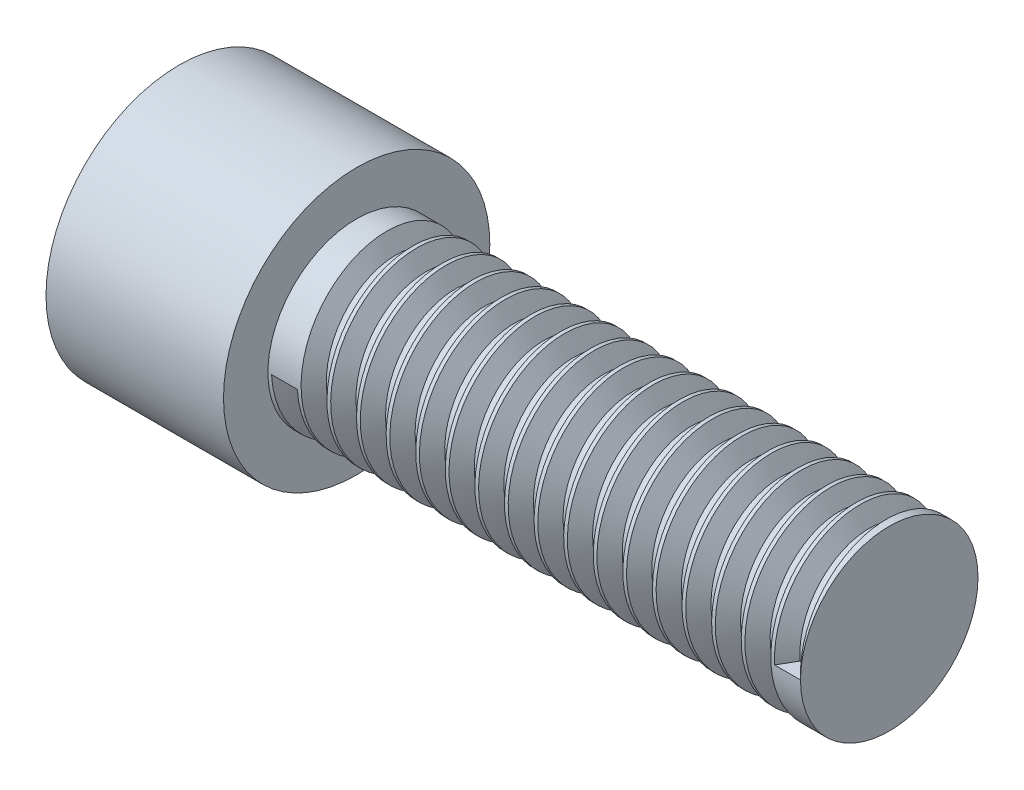
SolidWorks part; units mm, degrees
material "Pirinç"
ref_plane "Ön Düzlem" through (0, 0, 0) normal (0, 0, 1) x (1, 0, 0)
ref_plane "Üst Düzlem" through (0, 0, 0) normal (0, 1, 0) x (1, 0, 0)
ref_plane "Sağ Düzlem" through (0, 0, 0) normal (1, 0, 0) x (0, 0, -1)
sketch "Çizim1" plane through (0, 0, 0) normal (0, 0, 1) x (1, 0, 0)
  line L0 (14.4852, 0) -> (-14.4852, 0) construction
  line L1 (0, 0) -> (0, 3)
  line L2 (0, 3) -> (-18, 3)
  line L3 (-18, 3) -> (-18, 4.5)
  line L4 (-18, 4.5) -> (-24, 4.5)
  line L5 (-24, 4.5) -> (-24, 0)
  line L6 (0, 0) -> (-24, 0)
  point P4 (0, 0)
  dimension "D1" = 3
  dimension "D2" = 18
  dimension "D3" = 1.5
  dimension "D4" = 6
  dimension "D5" = 4.5
revolve "Döndür1" add sketch "Çizim1" angle 360 about L0
sketch "Çizim2" plane through (-24, 0, 0) normal (-1, 0, 0) x (0, 0, 1)
  line L1 (3, -1.7321) -> (3, 1.7321)
  line L2 (3, 1.7321) -> (0, 3.4641)
  line L3 (0, 3.4641) -> (-3, 1.7321)
  line L4 (-3, 1.7321) -> (-3, -1.7321)
  line L5 (-3, -1.7321) -> (0, -3.4641)
  line L6 (0, -3.4641) -> (3, -1.7321)
  circle A0 centre (0, 0) radius 3 construction
  dimension "D1" = 6
extrude "Kes-Ekstrüzyon1" cut sketch "Çizim2" against normal blind 4
thread "Diş1" pitch 1 method cut profile "Diş Profili1" start angle 0, offset 0, length 17, pitch 1, diameter 6
ref_plane "Düzlem1" through (0, 0, 3) normal (0, -1, 0) x (0, 0, 1)
sketch "Diş Profili1" plane through (0, 0, 3) normal (0, -1, 0) x (0, 0, 1)
  line L0 (0, 0) -> (0, 1) construction
  line L11 (0, 0) -> (0, 0.875)
  line L12 (0, 0.875) -> (-0.5413, 0.5625)
  line L13 (-0.5413, 0.5625) -> (-0.5413, 0.3125)
  line L15 (-0.5413, 0.3125) -> (0, 0)
  line L17 (-0.5413, 0.4375) -> (0, 0.4375) construction
  point P2 (0, 0)
  dimension "Pitch" = 1
  dimension "Profile_Angle" = 60
  dimension "Profile_Land" = 0.25
  dimension "Profile_Height" = 0.5413
